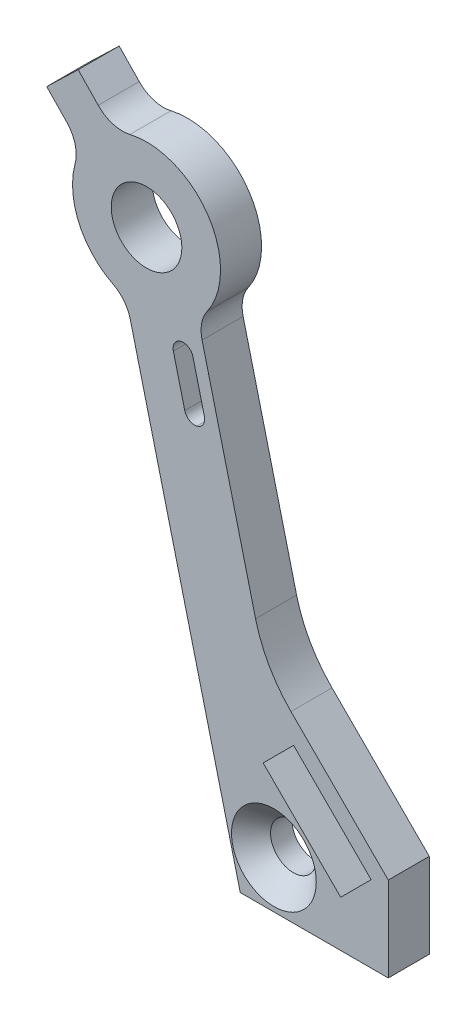
SolidWorks part; units mm, degrees
ref_plane "Front Plane" through (0, 0, 0) normal (0, 0, 1) x (1, 0, 0)
ref_plane "Top Plane" through (0, 0, 0) normal (0, 1, 0) x (1, 0, 0)
ref_plane "Right Plane" through (0, 0, 0) normal (1, 0, 0) x (0, 0, -1)
sketch "Sketch1" plane through (0, 0, 0) normal (0, 0, 1) x (1, 0, 0)
  line L0 (0, 11) -> (11, 0) construction
  line L1 (0, 0) -> (11, 0)
  line L2 (0, 0) -> (0, 11) construction
  line L3 (0, 11) -> (11, 11) construction
  line L4 (11, 0) -> (11, 11) construction
  line L5 (0, 0) -> (2.5, 0)
  line L6 (0, 0) -> (0, 3.5)
  line L7 (0, 3.5) -> (2.5, 3.5) construction
  line L8 (2.5, 0) -> (2.5, 3.5) construction
  line L9 (10.8939, 0) -> (10.947, 0.053) construction
  line L10 (7.4645, 3.4295) -> (1.7015, 9.1924)
  line L11 (1.7015, 9.1924) -> (3.9643, 11.4551)
  line L12 (7.4645, 3.4295) -> (9.7272, 5.6922)
  line L13 (3.9643, 11.4551) -> (9.7272, 5.6922)
  line L14 (0, 0) -> (-9.6331, 38.6679)
  line L15 (-9.6331, 38.6679) -> (-4.2962, 39.9974)
  line L16 (-4.2962, 39.9974) -> (1.8076, 15.4963)
  line L17 (1.8076, 15.4963) -> (11, 6.3039)
  line L18 (11, 0) -> (7.5175, 3.4825)
  line L19 (11, 6.3039) -> (11, 0)
  line L20 (0, 0) -> (0, 40.9886) construction
  line L21 (-6.9646, 39.3327) -> (-13.2153, 45.8079) construction
  line L22 (-14.3845, 44.6793) -> (-12.0462, 46.9365)
  line L23 (-12.0462, 46.9365) -> (-9.4448, 44.2417) construction
  line L24 (-14.3845, 44.6793) -> (-11.7831, 41.9845)
  line L25 (-12.0462, 46.9365) -> (-9.4448, 44.2417)
  line L27 (-5.1508, 33.0859) -> (-3.9421, 28.2342)
  line L28 (-3.9421, 28.2342) -> (-2.4866, 28.5968)
  line L29 (-2.4866, 28.5968) -> (-3.6953, 33.4485)
  line L30 (-3.6953, 33.4485) -> (-5.1508, 33.0859)
  line L31 (-7.4575, 29.9348) -> (-4.5464, 30.66) construction
  circle A0 centre (2.5, 3.5) radius 1.5
  circle A1 centre (-6.9646, 39.3327) radius 2.625
  circle A3 centre (-6.9646, 39.3327) radius 5.5
  point P28 (-13.2153, 45.8079)
  dimension "D5" = 3
  dimension "D6" = 5.25
  dimension "D7" = 11
  dimension "D1" = 11
  dimension "D2" = 11
  dimension "D3" = 3.5
  dimension "D4" = 2.5
  dimension "D8" = 45
  dimension "D9" = 6.3039
  dimension "D10" = 90
  dimension "D11" = 90
  dimension "D12" = 25.25
  dimension "D13" = 13
  dimension "D14" = 3.2
  dimension "D15" = 8.15
  dimension "D16" = 0.075
  dimension "D17" = 4.925
  dimension "D18" = 5.5
  dimension "D19" = 90
  dimension "D20" = 3.25
  dimension "D21" = 90
  dimension "D22" = 90
  dimension "D23" = 9
  dimension "D24" = 150
  dimension "D25" = 9
  dimension "D32" = 5
  dimension "D33" = 1.5
  dimension "D34" = 3
extrude "Boss-Extrude1" add sketch "Sketch1" along normal blind 3.05 contours A3 L14 L15 A1 L16 | L14 A3 L16 L15 A1 | A3 L14 L1 L12 L10 L11 L13 L19 L17 L16 A0 | L25 L22 L24 A3 | L24 A3 | A3 L14 region at (0.3238, 14.731, 0) region at (-11.9007, 37.2799, 0) region at (-6.1079, 35.8937, 0) region at (-11.9712, 44.5191, 0)
hole_wizard "CSK for M3 Flat Head Machine Screw1" positions "Sketch2" profile "Sketch3" countersink size "M3" standard "ANSI Metric" end condition through all
sketch "Sketch2" plane through (0, 0, 3.05) normal (0, 0, 1) x (1, 0, 0)
  point P0 (2.5, 3.5)
sketch "Sketch3" plane through (2.5, 3.5, 3.05) normal (1, 0, 0) x (0, -1, 0)
  line L0 (0, 0) -> (0, 3.05)
  line L1 (0, 3.05) -> (1.7, 3.05)
  line L2 (1.7, 3.05) -> (1.7, 1.45)
  line L3 (1.7, 1.45) -> (3.15, 0)
  line L5 (3.15, 0) -> (0, 0)
  line L6 (-1.7, 1.45) -> (-3.15, 0) construction
  line L11 (0, -6.35) -> (0, 107.95) construction
  dimension "Thru Hole Dia." = 3.4
  dimension "Thru Hole Depth" = 3.05
  dimension "Near C'Sink Dia." = 6.3
  dimension "Near C'Sink Angle" = 90
fillet "Fillet3" radius 2.5 4 edges at (-9.4448, 44.2417, 1.525) (-11.7831, 41.9845, 1.525) (-8.4817, 34.046, 1.525) (-3.1448, 35.3756, 1.525)
fillet "Fillet4" radius 10 1 edges at (1.8076, 15.4963, 1.525)
fillet "Fillet6" radius 0.75 4 edges at (-2.4866, 28.5968, 1.525) (-3.9421, 28.2342, 1.525) (-3.6953, 33.4485, 1.525) (-5.1508, 33.0859, 1.525)
